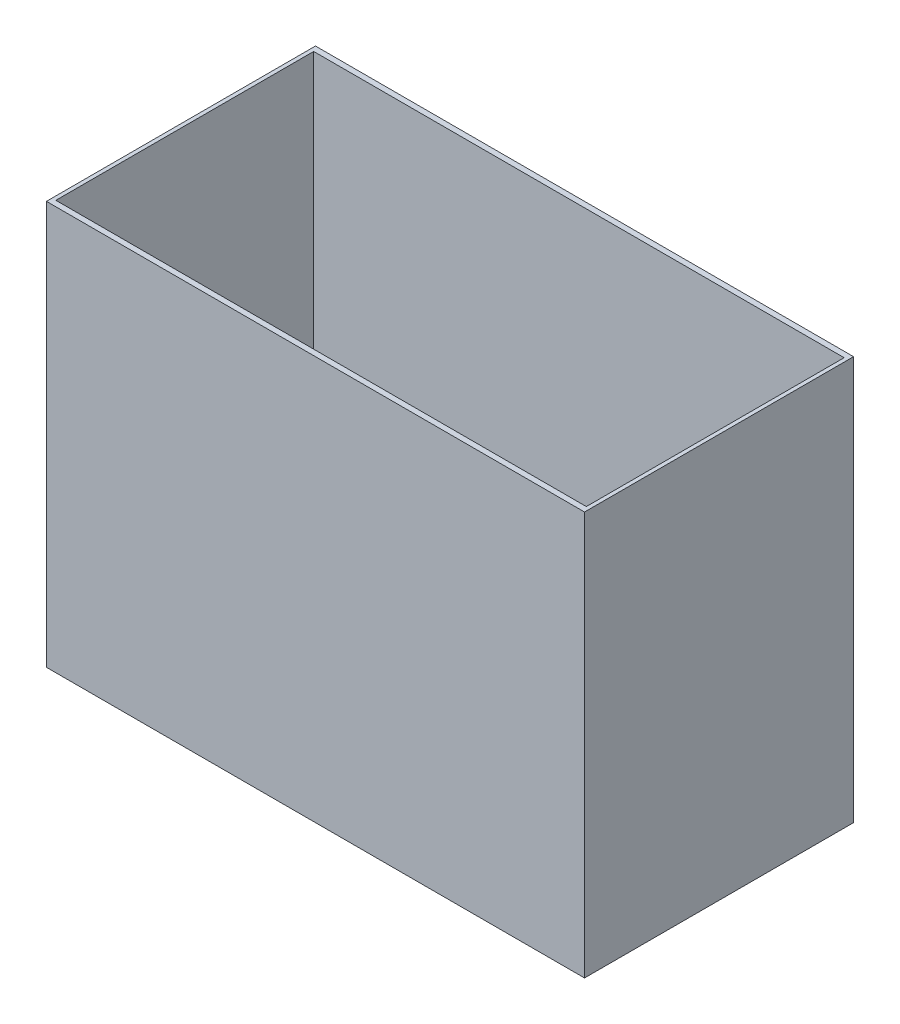
SolidWorks part; units mm, degrees
ref_plane "Front Plane" through (0, 0, 0) normal (0, 0, 1) x (1, 0, 0)
ref_plane "Top Plane" through (0, 0, 0) normal (0, 1, 0) x (1, 0, 0)
ref_plane "Right Plane" through (0, 0, 0) normal (1, 0, 0) x (0, 0, -1)
other "Bounding Box"
ref_plane "Default Plane" through (-292.1, 0, -139.7) normal (0, 1, 0) x (1, 0, 0)
sketch "Sketch1" plane through (0, 0, 0) normal (0, 1, 0) x (1, 0, 0)
  line L0 (-292.1, 0) -> (292.1, 0) construction
  line L1 (-292.1, 139.7) -> (292.1, 139.7)
  line L2 (-292.1, 139.7) -> (-292.1, -139.7)
  line L3 (-292.1, -139.7) -> (292.1, -139.7)
  line L4 (292.1, 139.7) -> (292.1, -139.7)
  line L5 (0, 139.7) -> (0, -139.7) construction
  point P8 (0, 0)
  dimension "D1" = 584.2
  dimension "D2" = 279.4
extrude "Boss-Extrude1" add sketch "Sketch1" along normal blind 12.7
sketch "Sketch2" plane through (0, 12.7, 0) normal (0, 1, 0) x (1, 0, 0)
  line L0 (-245.9259, -63.5) -> (-55.3589, -63.5) construction
  line L1 (-241.3, -120.6497) -> (-152.4, -120.6497)
  line L2 (-241.3, -120.6497) -> (-241.3, -101.5997)
  line L3 (-241.3, -101.5997) -> (-152.4, -101.5997)
  line L4 (-152.4, -120.6497) -> (-152.4, -101.5997)
  line L5 (-241.3, -120.6497) -> (-152.4, -101.5997) construction
  line L6 (-241.3, -101.5997) -> (-152.4, -120.6497) construction
  line L7 (-292.1, 139.7) -> (-292.1, -139.7) construction
  line L8 (-292.1, 0) -> (292.1, 0) construction
  line L9 (292.1, -139.7) -> (292.1, 139.7) construction
  line L10 (0, 0) -> (0, 121.6784) construction
  line L11 (241.3, -101.5997) -> (152.4, -120.6497) construction
  line L12 (241.3, -120.6497) -> (152.4, -101.5997) construction
  line L13 (152.4, -120.6497) -> (152.4, -101.5997)
  line L14 (241.3, -101.5997) -> (152.4, -101.5997)
  line L15 (241.3, -120.6497) -> (241.3, -101.5997)
  line L16 (241.3, -120.6497) -> (152.4, -120.6497)
  point P0 (-196.85, -111.1247)
  point P17 (196.85, -111.1247)
  dimension "D1" = 19.05
  dimension "D2" = 88.9
  dimension "D3" = 38.0997
  dimension "D4" = 50.8
  dimension "D5" = 63.5
extrude "Boss-Extrude2" [suppressed] add sketch "Sketch2" along normal blind 304.8 separate body contours L2 L1 L4 L3
pattern_linear "LPattern1" [suppressed] count 2 spacing 304.8 of bodies 101
pattern_linear "LPattern2" [suppressed] count 2 spacing 215.9 of bodies 101
sketch "Sketch3" plane through (0, 0, 0) normal (0, 1, 0) x (1, 0, 0)
  line L1 (-304.8, -152.4) -> (304.8, -152.4)
  line L2 (-304.8, -152.4) -> (-304.8, 152.4)
  line L3 (-304.8, 152.4) -> (304.8, 152.4)
  line L4 (304.8, -152.4) -> (304.8, 152.4)
  line L5 (-304.8, -152.4) -> (304.8, 152.4) construction
  line L6 (-304.8, 152.4) -> (304.8, -152.4) construction
  line L7 (-300.482, -146.05) -> (300.482, -146.05)
  line L8 (-300.482, -146.05) -> (-300.482, 146.05)
  line L9 (-300.482, 146.05) -> (300.482, 146.05)
  line L10 (300.482, -146.05) -> (300.482, 146.05)
  line L11 (-300.482, -146.05) -> (300.482, 146.05) construction
  line L12 (-300.482, 146.05) -> (300.482, -146.05) construction
  point P0 (0, 0)
  point P6 (0, 0)
  dimension "D1" = 609.6
  dimension "D2" = 304.8
  dimension "D3" = 292.1
  dimension "D4" = 600.964
extrude "Boss-Extrude3" add sketch "Sketch3" along normal blind 457.2 separate body
sketch "Sketch4" plane through (0, 12.7, 0) normal (0, 1, 0) x (1, 0, 0)
  circle A0 centre (273.05, 120.65) radius 2.7781
  circle A1 centre (273.05, 120.65) radius 2.7781 construction
  dimension "D1" = 5.5562
extrude "Cut-Extrude1" cut sketch "Sketch4" against normal through all
mirror "Mirror1" about plane through (0, 0, 0) normal (0, 0, 1) of "Cut-Extrude1"
